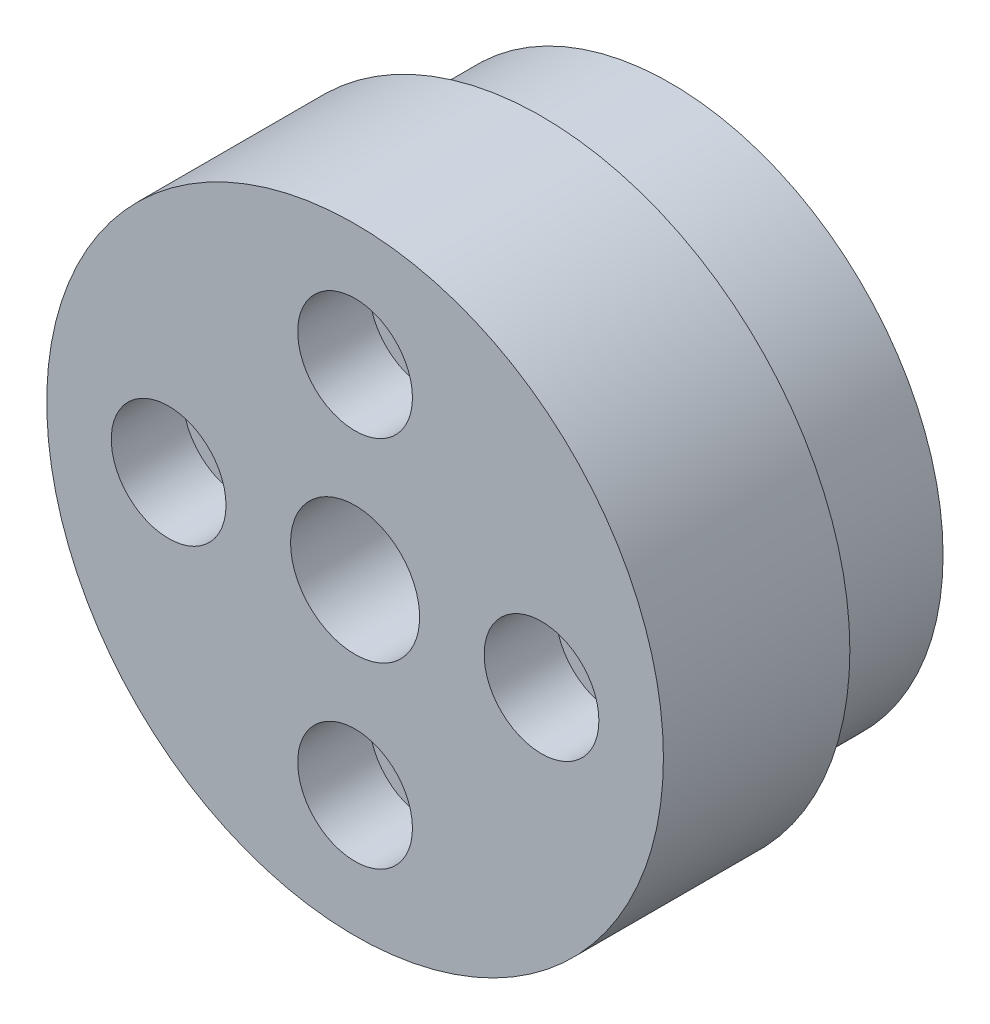
SolidWorks part; units mm, degrees
ref_plane "Front Plane" through (0, 0, 0) normal (0, 0, 1) x (1, 0, 0)
ref_plane "Top Plane" through (0, 0, 0) normal (0, 1, 0) x (1, 0, 0)
ref_plane "Right Plane" through (0, 0, 0) normal (1, 0, 0) x (0, 0, -1)
sketch "Sketch1" plane through (0, 0, 0) normal (0, 0, 1) x (1, 0, 0)
  circle A0 centre (0, 0) radius 10.75
  circle A1 centre (0, 0) radius 9.5
  dimension "D1" = 19
  dimension "25" = 21.5
extrude "Boss-Extrude1" add sketch "Sketch1" against normal blind 11 contours A1 region at (0, 0, 0)
extrude "Boss-Extrude2" add sketch "Sketch1<3>" against normal blind 6.5 contours A0 A1 region at (-10.4459, 0, 0)
sketch "Sketch1<3>" plane through (0, 0, 0) normal (0, 0, 1) x (1, 0, 0) same geometry as "Sketch1"
sketch "Sketch3" plane through (0, 0, -11) normal (0, 0, -1) x (-1, 0, 0)
  circle A0 centre (-6.5, 0) radius 1.35
  circle A1 centre (0, 6.5) radius 1.35
  circle A2 centre (6.5, 0) radius 1.35
  circle A3 centre (0, -6.5) radius 1.35
  circle A4 centre (-6.5, 0) radius 2
  circle A5 centre (0, 6.5) radius 2
  circle A6 centre (6.5, 0) radius 2
  circle A7 centre (0, -6.5) radius 2
  dimension "D1" = 2.7
  dimension "D3" = 4
  dimension "D4" = 4
  dimension "D2" = 6.5
  dimension "D5" = 4
extrude "Cut-Extrude2" cut sketch "Sketch3" against normal through all contours A1 | A0 | A2 | A3 region at (6.5, 0, -11) region at (0, 6.5, -11) region at (-6.5, 0, -11) region at (0, -6.5, -11)
sketch "Sketch4" plane through (0, 0, -11) normal (0, 0, -1) x (-1, 0, 0)
  circle A0 centre (0, 0) radius 2.25
  dimension "D1" = 4.5
extrude "Cut-Extrude4" cut sketch "Sketch4" against normal through all
extrude "Cut-Extrude5" cut sketch "Sketch3<4>" along normal blind 2.5 from surface starting at face at (-2.25, 0, 0)
sketch "Sketch3<4>" plane through (0, 0, -11) normal (0, 0, -1) x (-1, 0, 0) same geometry as "Sketch3"
